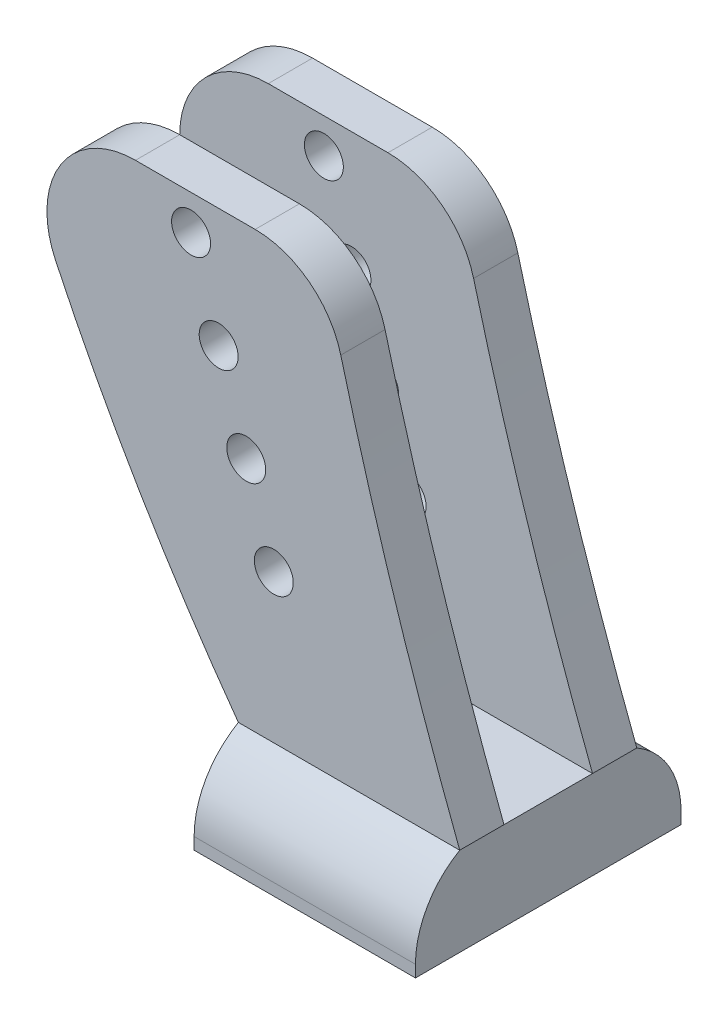
SolidWorks part; units mm, degrees
ref_plane "前视基准面" through (0, 0, 0) normal (0, 0, 1) x (1, 0, 0)
ref_plane "上视基准面" through (0, 0, 0) normal (0, 1, 0) x (1, 0, 0)
ref_plane "右视基准面" through (0, 0, 0) normal (1, 0, 0) x (0, 0, -1)
other "Configuration Table"
sketch "Sketch1" plane through (0, 0, 0) normal (0, 1, 0) x (1, 0, 0)
  line L1 (-6.25, -7.5) -> (6.25, -7.5)
  line L2 (-6.25, -7.5) -> (-6.25, 7.5)
  line L3 (-6.25, 7.5) -> (6.25, 7.5)
  line L4 (6.25, -7.5) -> (6.25, 7.5)
  line L5 (-6.25, -7.5) -> (6.25, 7.5) construction
  line L6 (-6.25, 7.5) -> (6.25, -7.5) construction
  point P0 (0, 0)
  dimension "D1" = 12.5
  dimension "D2" = 15
extrude "Boss-Extrude1" add sketch "Sketch1" along normal blind 5
sketch "Sketch10" plane through (0, 5, 0) normal (0, 1, 0) x (1, 0, 0)
  line L0 (0, 0) -> (0, 5) construction
  line L1 (0, 5) -> (6.25, 5) construction
  dimension "D1" = 5
  dimension "D2" = 6.25
ref_plane "Plane2" through (0, 0, -5) normal (0, 0, -1) x (-1, 0, 0)
sketch "Sketch12" plane through (0, 0, -5) normal (0, 0, -1) x (-1, 0, 0)
  line L0 (7.0182, 75.2376) -> (27.0182, 75.2376)
  line L1 (27.0182, 75.2376) -> (17.0182, 75.2376)
  line L2 (17.0182, 75.2376) -> (17.0182, 53.6178) construction
  line L3 (17.0182, 75.2376) -> (-17.1838, -18.7317) construction
  line L4 (-6.25, 5) -> (6.25, 5)
  line L5 (1.4079, 29.5864) -> (19.6579, 29.5864)
  line L6 (-3.2505, 13.3692) -> (11.7495, 13.3692) construction
  line L7 (4.2915, 43.7033) -> (24.0915, 43.7033) construction
  line L8 (6.0915, 57.3639) -> (26.4915, 57.3639) construction
  line L9 (4.2495, 13.3692) -> (14.1915, 43.7033) construction
  arc A0 (27.0182, 75.2376) -> (-17.1838, -18.7317) centre (-82.8336, 69.5299) cw
  arc A1 (7.0182, 75.2376) -> (-17.1838, -18.7317) centre (-192.9769, 76.6455) cw
  circle A2 centre (4.2495, 13.3692) radius 1.1
  circle A3 centre (16.2915, 57.3639) radius 2
  circle A4 centre (14.1915, 43.7033) radius 2
  arc A5 (14.2915, 57.3639) -> (12.1915, 43.7033) centre (-63.5497, 62.3385) cw
  arc A6 (18.2915, 57.3639) -> (16.1915, 43.7033) centre (-51.6078, 61.1176) cw
  circle A7 centre (5.8068, 18.1205) radius 1.1
  circle A8 centre (7.364, 22.8718) radius 1.1
  circle A9 centre (8.9213, 27.6231) radius 1.1
  circle A10 centre (10.4785, 32.3745) radius 1.1
  circle A11 centre (12.0357, 37.1258) radius 1.1
  dimension "D3" = 110
  dimension "D4" = 200
  dimension "D10" = 4
  dimension "D11" = 4
  dimension "D12" = 2.2
  dimension "D13" = 78
  dimension "D14" = 70
  dimension "D1" = 20
  dimension "D2" = 100
  dimension "D5" = 12.5
  dimension "D6" = 18.25
  dimension "D7" = 15
  dimension "D8" = 20.4
  dimension "D9" = 19.8
  dimension "D15" = 6
extrude "Boss-Extrude3" add sketch "Sketch12" against normal blind 10 contours L5 A1 L4 A0 region at (-10.5329, 29.2292, -5)
sketch "Sketch13" plane through (0, 29.5864, 0) normal (0, 1, 0) x (1, 0, 0)
  line L1 (-20, -2.5) -> (20, -2.5)
  line L2 (-20, -2.5) -> (-20, 2.5)
  line L3 (-20, 2.5) -> (20, 2.5)
  line L4 (20, -2.5) -> (20, 2.5)
  line L5 (-20, -2.5) -> (20, 2.5) construction
  line L6 (-20, 2.5) -> (20, -2.5) construction
  point P0 (0, 0)
  dimension "D1" = 5
  dimension "D2" = 40
extrude "Cut-Extrude2" cut sketch "Sketch13" against normal up to surface (24.5864 mm away) up to face at (0, 5, 6.25)
fillet "Fillet2" radius 5 6 edges at (-19.6579, 29.5864, 3.75) (-1.4079, 29.5864, 3.75) (-1.4079, 29.5864, -3.75) (-19.6579, 29.5864, -3.75) (0, 5, -7.5) (0, 5, 7.5)
